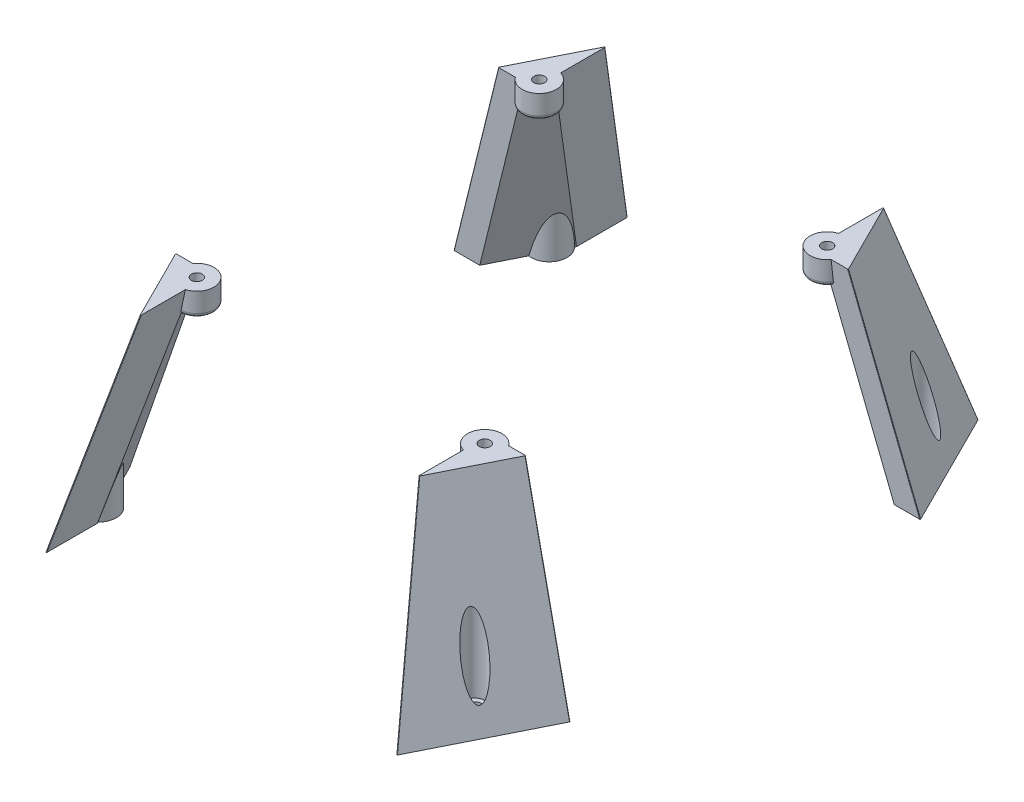
SolidWorks part; units mm, degrees
material "ABS"
ref_plane "Front Plane" through (0, 0, 0) normal (0, 0, 1) x (1, 0, 0)
ref_plane "Top Plane" through (0, 0, 0) normal (0, 1, 0) x (1, 0, 0)
ref_plane "Right Plane" through (0, 0, 0) normal (1, 0, 0) x (0, 0, -1)
sketch "Sketch1" plane through (0, 0, 0) normal (0, 1, 0) x (1, 0, 0)
  line L1 (-60, 75) -> (60, 75)
  line L2 (-60, 75) -> (-60, -75)
  line L3 (-60, -75) -> (60, -75)
  line L4 (60, 75) -> (60, -75)
  line L5 (-60, 75) -> (60, -75) construction
  line L6 (-60, -75) -> (60, 75) construction
  point P0 (0, 0)
  dimension "D1" = 120
  dimension "D2" = 150
extrude "Boss-Extrude1" add sketch "Sketch1" along normal mid plane 6
sketch "Sketch2" plane through (0, 0, 0) normal (0, 0, 1) x (1, 0, 0)
  line L0 (-60, -3) -> (-60, -17.5588)
  line L1 (-60, -17.5588) -> (-20, -3)
  line L2 (-60, -3) -> (60, -3) construction
  line L3 (-20, -3) -> (-60, -3)
  line L4 (0, 3) -> (0, -3) construction
  line L5 (-60, 3) -> (60, 3) construction
  line L6 (20, -3) -> (60, -3)
  line L7 (60, -17.5588) -> (20, -3)
  line L8 (60, -3) -> (60, -17.5588)
  dimension "D1" = 40
  dimension "D2" = 20
extrude "Boss-Extrude2" add sketch "Sketch2" along normal up to surface and the other way up to surface up to face at (0, 0, 75) other way up to face at (0, 0, -75)
sketch "Sketch3" plane through (0, 0, 0) normal (0, 0, 1) x (1, 0, 0)
  line L0 (-20, -3) -> (-46.3142, -3)
  line L1 (-46.3142, -3) -> (-60, -7.9812)
  line L2 (-60, 3) -> (-60, -17.5588) construction
  line L3 (-60, -7.9812) -> (-60, -13.3021)
  line L4 (-60, -13.3021) -> (-45.4326, -8)
  line L5 (-45.4326, -8) -> (-33.7374, -8)
  line L6 (-20, -3) -> (-60, -17.5588) construction
  line L7 (-33.7374, -8) -> (-20, -3)
  line L8 (0, 3) -> (0, -3) construction
  line L9 (-60, 3) -> (60, 3) construction
  line L10 (-20, -3) -> (20, -3) construction
  line L11 (33.7374, -8) -> (20, -3)
  line L12 (45.4326, -8) -> (33.7374, -8)
  line L13 (60, -13.3021) -> (45.4326, -8)
  line L14 (60, -7.9812) -> (60, -13.3021)
  line L15 (46.3142, -3) -> (60, -7.9812)
  line L16 (20, -3) -> (46.3142, -3)
  dimension "D1" = 5
  dimension "D2" = 5
  dimension "D3" = 4
extrude "Cut-Extrude1" cut sketch "Sketch3" along normal blind 50.8 from offset 18
mirror "Mirror1" about plane through (0, 0, 0) normal (0, 0, 1) of "Cut-Extrude1"
ref_plane "Plane1" through (0, 53, 0) normal (0, 1, 0) x (1, 0, 0)
sketch "Sketch5" plane through (0, 3, 0) normal (0, 1, 0) x (1, 0, 0)
  line L0 (-60, 0) -> (60, 0) construction
  line L1 (-60, 75) -> (-60, -75) construction
  line L2 (60, -75) -> (60, 75) construction
  line L3 (0, 75) -> (0, -75) construction
  line L4 (60, 75) -> (-60, 75) construction
  line L5 (-60, -75) -> (60, -75) construction
  line L6 (-60, -75) -> (-60, -45)
  line L7 (-60, -45) -> (-45, -75)
  line L8 (-45, -75) -> (-60, -75)
  line L9 (45, -75) -> (60, -75)
  line L10 (60, -45) -> (45, -75)
  line L11 (60, -75) -> (60, -45)
  line L12 (60, 75) -> (60, 45)
  line L13 (60, 45) -> (45, 75)
  line L14 (45, 75) -> (60, 75)
  line L15 (-45, 75) -> (-60, 75)
  line L16 (-60, 45) -> (-45, 75)
  line L17 (-60, 75) -> (-60, 45)
  dimension "D1" = 15
  dimension "D2" = 30
extrude "Cut-Extrude2" cut sketch "Sketch5" against normal through all
sketch "Sketch4" plane through (0, 53, 0) normal (0, 1, 0) x (1, 0, 0)
  line L0 (-35.7295, 60) -> (-45, 41.459)
  line L5 (-45, 41.459) -> (-45, -41.459)
  line L6 (-45, -41.459) -> (-35.7295, -60)
  line L7 (-35.7295, -60) -> (35.7295, -60)
  line L8 (35.7295, -60) -> (45, -41.459)
  line L9 (45, -41.459) -> (45, 41.459)
  line L10 (45, 41.459) -> (35.7295, 60)
  line L11 (35.7295, 60) -> (-35.7295, 60)
  line L12 (-45, 75) -> (-60, 45)
  line L13 (-60, 45) -> (-60, -45)
  line L14 (-60, -45) -> (-45, -75)
  line L15 (-45, -75) -> (45, -75)
  line L16 (45, -75) -> (60, -45)
  line L17 (60, -45) -> (60, 45)
  line L18 (60, 45) -> (45, 75)
  line L19 (45, 75) -> (-45, 75)
  line L20 (-45, 75) -> (-60, 45) construction
  line L21 (-60, 45) -> (-60, -45) construction
  line L22 (-60, -45) -> (-45, -75) construction
  line L23 (-45, -75) -> (45, -75) construction
  line L24 (45, -75) -> (60, -45) construction
  line L25 (60, -45) -> (60, 45) construction
  line L26 (60, 45) -> (45, 75) construction
  line L27 (45, 75) -> (-45, 75) construction
  dimension "D1" = 0
  dimension "D2" = 15
extrude "Boss-Extrude3" add sketch "Sketch4" along normal blind 4 separate body
sketch "Sketch6" plane through (0, 3, 0) normal (0, 1, 0) x (1, 0, 0)
  line L0 (-60, 0) -> (60, 0) construction
  line L1 (-60, 45) -> (-60, -45) construction
  line L2 (60, -45) -> (60, 45) construction
  line L3 (0, 75) -> (0, -75) construction
  line L4 (45, 75) -> (-45, 75) construction
  line L5 (-45, -75) -> (45, -75) construction
  line L6 (-60, -45) -> (-53.2918, -45)
  line L7 (-53.2918, -45) -> (-45, -61.5836)
  line L8 (-45, -61.5836) -> (-45, -75)
  line L9 (-45, -75) -> (-60, -45) construction
  line L10 (-45, -75) -> (-60, -45)
  line L11 (45, -75) -> (60, -45)
  line L12 (45, -61.5836) -> (45, -75)
  line L13 (53.2918, -45) -> (45, -61.5836)
  line L14 (60, -45) -> (53.2918, -45)
  line L15 (60, 45) -> (53.2918, 45)
  line L16 (53.2918, 45) -> (45, 61.5836)
  line L17 (45, 61.5836) -> (45, 75)
  line L18 (45, 75) -> (60, 45)
  line L19 (-45, 75) -> (-60, 45)
  line L20 (-45, 61.5836) -> (-45, 75)
  line L21 (-53.2918, 45) -> (-45, 61.5836)
  line L22 (-60, 45) -> (-53.2918, 45)
  dimension "D1" = 6
sketch "Sketch7" plane through (0, 53, 0) normal (0, -1, 0) x (-1, 0, 0)
  line L0 (35.7295, -60) -> (35.7295, -46.5836)
  line L1 (35.7295, -46.5836) -> (38.2918, -41.459)
  line L2 (38.2918, -41.459) -> (45, -41.459)
  line L3 (45, -41.459) -> (35.7295, -60)
  line L4 (60, 0) -> (-60, 0) construction
  line L5 (0, 75) -> (0, -75) construction
  line L6 (60, 0) -> (-60, 0) construction
  line L7 (0, 75) -> (0, -75) construction
  line L8 (-45, -41.459) -> (-35.7295, -60)
  line L9 (-38.2918, -41.459) -> (-45, -41.459)
  line L10 (-35.7295, -46.5836) -> (-38.2918, -41.459)
  line L11 (-35.7295, -60) -> (-35.7295, -46.5836)
  line L12 (-35.7295, 60) -> (-35.7295, 46.5836)
  line L13 (-35.7295, 46.5836) -> (-38.2918, 41.459)
  line L14 (-38.2918, 41.459) -> (-45, 41.459)
  line L15 (-45, 41.459) -> (-35.7295, 60)
  line L16 (45, 41.459) -> (35.7295, 60)
  line L17 (38.2918, 41.459) -> (45, 41.459)
  line L18 (35.7295, 46.5836) -> (38.2918, 41.459)
  line L19 (35.7295, 60) -> (35.7295, 46.5836)
  dimension "D1" = 6
loft "Loft3" add section "Sketch6" section "Sketch7" connector at (-45, 3, 61.5836) connector at (-35.7295, 53, 46.5836)
mirror "Mirror2" about plane through (0, 0, 0) normal (1, 0, 0) of "Loft3"
mirror "Mirror3" about plane through (0, 0, 0) normal (0, 0, 1) of "Loft3", "Mirror2"
sketch "Sketch8" plane through (0, 57, 0) normal (0, 1, 0) x (1, 0, 0)
  line L8 (35.7295, 60) -> (-35.7295, 60)
  line L9 (-35.7295, 60) -> (-45, 41.459)
  line L10 (-45, 41.459) -> (-45, -41.459)
  line L11 (-45, -41.459) -> (-35.7295, -60)
  line L12 (-35.7295, -60) -> (35.7295, -60)
  line L13 (35.7295, -60) -> (45, -41.459)
  line L14 (45, -41.459) -> (45, 41.459)
  line L15 (45, 41.459) -> (35.7295, 60)
  line L16 (35.7295, 60) -> (-35.7295, 60)
  line L17 (-35.7295, 60) -> (-45, 41.459)
  line L18 (-45, 41.459) -> (-45, -41.459)
  line L19 (-45, -41.459) -> (-35.7295, -60)
  line L20 (-35.7295, -60) -> (35.7295, -60)
  line L21 (35.7295, -60) -> (45, -41.459)
  line L22 (45, -41.459) -> (45, 41.459)
  line L23 (45, 41.459) -> (35.7295, 60)
  dimension "D1" = 0
extrude "Cut-Extrude3" cut sketch "Sketch8" against normal up to surface (4 mm away) up to face at (0, 53, 0)
sketch "Sketch9" plane through (0, 3, 0) normal (0, 1, 0) x (1, 0, 0)
  line L0 (60, -45) -> (45, -75) construction
  line L1 (-45, -75) -> (-60, -45) construction
  line L2 (-45, -75) -> (45, -75) construction
  line L3 (60, -45) -> (60, 45) construction
  line L4 (45, 75) -> (60, 45) construction
  line L5 (45, 75) -> (-45, 75) construction
  line L6 (-60, 45) -> (-45, 75) construction
  line L7 (-60, 45) -> (-60, -45) construction
  line L8 (60, -45) -> (45, -75)
  line L9 (-45, -75) -> (-60, -45)
  line L10 (-45, -75) -> (45, -75)
  line L11 (60, -45) -> (60, 45)
  line L12 (45, 75) -> (60, 45)
  line L13 (45, 75) -> (-45, 75)
  line L14 (-60, 45) -> (-45, 75)
  line L15 (-60, 45) -> (-60, -45)
extrude "Cut-Extrude4" cut sketch "Sketch9" against normal through all
sketch "Sketch10" plane through (0, 53, 0) normal (0, 1, 0) x (1, 0, 0)
  line L0 (-35.7295, -46.5836) -> (-38.2918, -41.459) construction
  line L1 (0, -38.8074) -> (0, 38.8074) construction
  line L2 (-38.8074, 0) -> (38.8074, 0) construction
  circle A0 centre (-37.0106, -44.0213) radius 1.4
  circle A1 centre (-37.0106, -44.0213) radius 4.4
  circle A2 centre (37.0106, -44.0213) radius 4.4
  circle A3 centre (37.0106, -44.0213) radius 1.4
  circle A4 centre (37.0106, 44.0213) radius 1.4
  circle A5 centre (37.0106, 44.0213) radius 4.4
  circle A6 centre (-37.0106, 44.0213) radius 4.4
  circle A7 centre (-37.0106, 44.0213) radius 1.4
  line M2 (-35.7295, -46.5836) -> (-38.2918, -41.459)
  dimension "D1" = 2.8
  dimension "D2" = 3
extrude "Boss-Extrude4" add sketch "Sketch10" against normal blind 6
extrude "Cut-Extrude5" cut sketch "Sketch10<2>" against normal through all contours A0 M2 | A0 M2 | A3 | A4 | A7 region at (-36.4792, 53, 43.7556) region at (-37.5421, 53, 44.287) region at (37.0106, 53, 44.0213) region at (37.0106, 53, -44.0213) region at (-37.0106, 53, -44.0213)
sketch "Sketch10<2>" plane through (0, 53, 0) normal (0, 1, 0) x (1, 0, 0) same geometry as "Sketch10"
fillet "Fillet1" radius 1 1 edges at (-33.2617, 47, 41.7179)
fillet "Fillet2" radius 1 1 edges at (-33.2617, 47, -41.7179)
fillet "Fillet3" radius 1 1 edges at (33.2617, 47, -41.7179)
fillet "Fillet4" radius 1 1 edges at (33.2617, 47, 41.7179)
sketch "Sketch12" plane through (0, 3, 0) normal (0, -1, 0) x (1, 0, 0)
  line L0 (-45, 75) -> (-60, 45) construction
  line L1 (0, -27.5002) -> (0, 27.5002) construction
  line L2 (27.5002, 0) -> (-27.5002, 0) construction
  line L3 (-53.2918, -45) -> (-45, -61.5836) construction
  line L4 (-53.2918, 45) -> (-45, 61.5836) construction
  line L5 (53.2918, 45) -> (45, 61.5836) construction
  line L6 (53.2918, -45) -> (45, -61.5836) construction
  line L7 (-49.093, -53.3975) -> (-45.1738, -61.2359)
  line L8 (-49.093, 53.3975) -> (-45.1738, 61.2359)
  line L9 (49.093, 53.3975) -> (45.1738, 61.2359)
  line L10 (49.093, -53.3975) -> (45.1738, -61.2359)
  circle A0 centre (-48.3856, 57.9428) radius 1.6
  circle A1 centre (-48.3856, 57.9428) radius 4.6
  circle A2 centre (48.3856, 57.9428) radius 4.6
  circle A3 centre (48.3856, 57.9428) radius 1.6
  circle A4 centre (48.3856, -57.9428) radius 1.6
  circle A5 centre (48.3856, -57.9428) radius 4.6
  circle A6 centre (-48.3856, -57.9428) radius 4.6
  circle A7 centre (-48.3856, -57.9428) radius 1.6
  point P6 (-52.5, 60)
  point P12 (52.5, 60)
  point P21 (52.5, -60)
  point P22 (-52.5, -60)
  line M2 (-53.2918, 45) -> (-45, 61.5836)
  dimension "D1" = 3.2
  dimension "D2" = 3
extrude "Boss-Extrude5" add sketch "Sketch12" against normal up to surface contours A1 A0 M2 region at (-45.9342, 3, 56.7171) up to face at (-44.5601, 25.0252, 47.6884)
extrude "Boss-Extrude7" add sketch "Sketch12<6>" against normal up to surface contours L9 A3 A2 region at (45.9342, 3, 56.7171) up to face at (42.0349, 32.4068, 47.7872)
sketch "Sketch12<6>" plane through (0, 3, 0) normal (0, -1, 0) x (1, 0, 0) same geometry as "Sketch12"
extrude "Boss-Extrude8" add sketch "Sketch12<7>" against normal up to surface contours L10 A5 A4 region at (45.9342, 3, -56.7171) up to face at (44.5601, 25.0252, -47.6884)
sketch "Sketch12<7>" plane through (0, 3, 0) normal (0, -1, 0) x (1, 0, 0) same geometry as "Sketch12"
extrude "Boss-Extrude9" add sketch "Sketch12<8>" against normal up to surface contours L7 A7 A6 region at (-45.9342, 3, -56.7171) up to face at (-42.0349, 32.4068, -47.7872)
sketch "Sketch12<8>" plane through (0, 3, 0) normal (0, -1, 0) x (1, 0, 0) same geometry as "Sketch12"
extrude "Cut-Extrude6" cut sketch "Sketch12<3>" against normal through all contours A0 M2 | A0 M2 | L10 A4 | L10 A4 | A7 L7 | A7 L7 | A3 region at (-47.0615, 3, -57.2807) region at (-48.421, 3, -57.9605) region at (-48.421, 3, 57.9605) region at (-47.0615, 3, 57.2807) region at (48.421, 3, -57.9605) region at (47.0615, 3, -57.2807)
sketch "Sketch12<3>" plane through (0, 3, 0) normal (0, -1, 0) x (1, 0, 0) same geometry as "Sketch12"
sketch "Sketch13" plane through (0, 3, 0) normal (0, -1, 0) x (1, 0, 0)
  line L0 (0, -27.5002) -> (0, 27.5002) construction
  line L1 (27.5002, 0) -> (-27.5002, 0) construction
  circle A0 centre (-48.3856, 57.9428) radius 2.75
  circle A1 centre (48.3856, 57.9428) radius 2.75
  circle A2 centre (48.3856, -57.9428) radius 2.75
  circle A3 centre (-48.3856, -57.9428) radius 2.75
  dimension "D1" = 5.5
extrude "Cut-Extrude7" cut sketch "Sketch13" against normal through all from offset 4 offset against normal yes
fillet "Fillet5" radius 0.1 2 edges
fillet "Fillet6" radius 0.1 2 edges at (-40.3647, 28, -67.5) (-52.5, 28, -43.2295)
fillet "Fillet7" radius 0.1 2 edges at (52.5, 28, -43.2295) (40.3647, 28, -67.5)
fillet "Fillet8" radius 0.1 2 edges at (40.3647, 28, 67.5) (52.5, 28, 43.2295)
